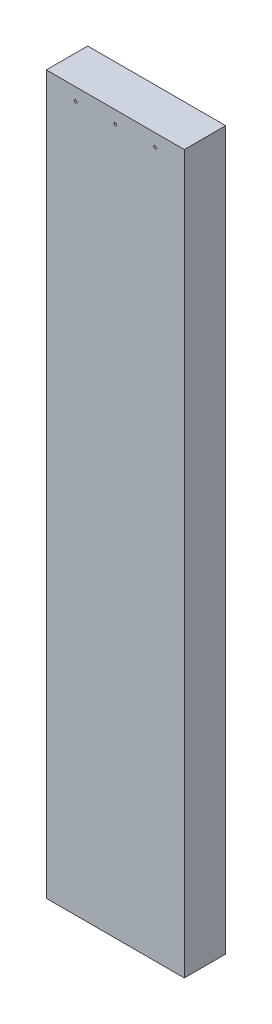
SolidWorks part; units mm, degrees
ref_plane "Front Plane" through (0, 0, 0) normal (0, 0, 1) x (1, 0, 0)
ref_plane "Top Plane" through (0, 0, 0) normal (0, 1, 0) x (1, 0, 0)
ref_plane "Right Plane" through (0, 0, 0) normal (1, 0, 0) x (0, 0, -1)
sketch "Sketch1" plane through (0, 0, 0) normal (0, 1, 0) x (1, 0, 0)
  line L1 (0, 0) -> (63.5, 0)
  line L2 (0, 0) -> (0, 19.05)
  line L3 (0, 19.05) -> (63.5, 19.05)
  line L4 (63.5, 0) -> (63.5, 19.05)
  dimension "D1" = 19.05
  dimension "D2" = 63.5
extrude "Boss-Extrude1" add sketch "Sketch1" along normal blind 330.2
sketch "Sketch2" plane through (0, 0, 0) normal (0, 0, 1) x (1, 0, 0)
  line L0 (13.462, 324.358) -> (50.038, 324.358) construction
  line L1 (0, 330.2) -> (63.5, 330.2) construction
  line L2 (31.75, 330.2) -> (31.75, 226.7643) construction
  circle A0 centre (13.462, 324.358) radius 0.635
  circle A1 centre (31.75, 324.358) radius 0.635
  circle A2 centre (50.038, 324.358) radius 0.635
  point P6 (31.75, 324.358)
  dimension "D3" = 1.27
  dimension "D1" = 5.842
  dimension "D2" = 36.576
extrude "Cut-Extrude1" cut sketch "Sketch2" against normal through all
